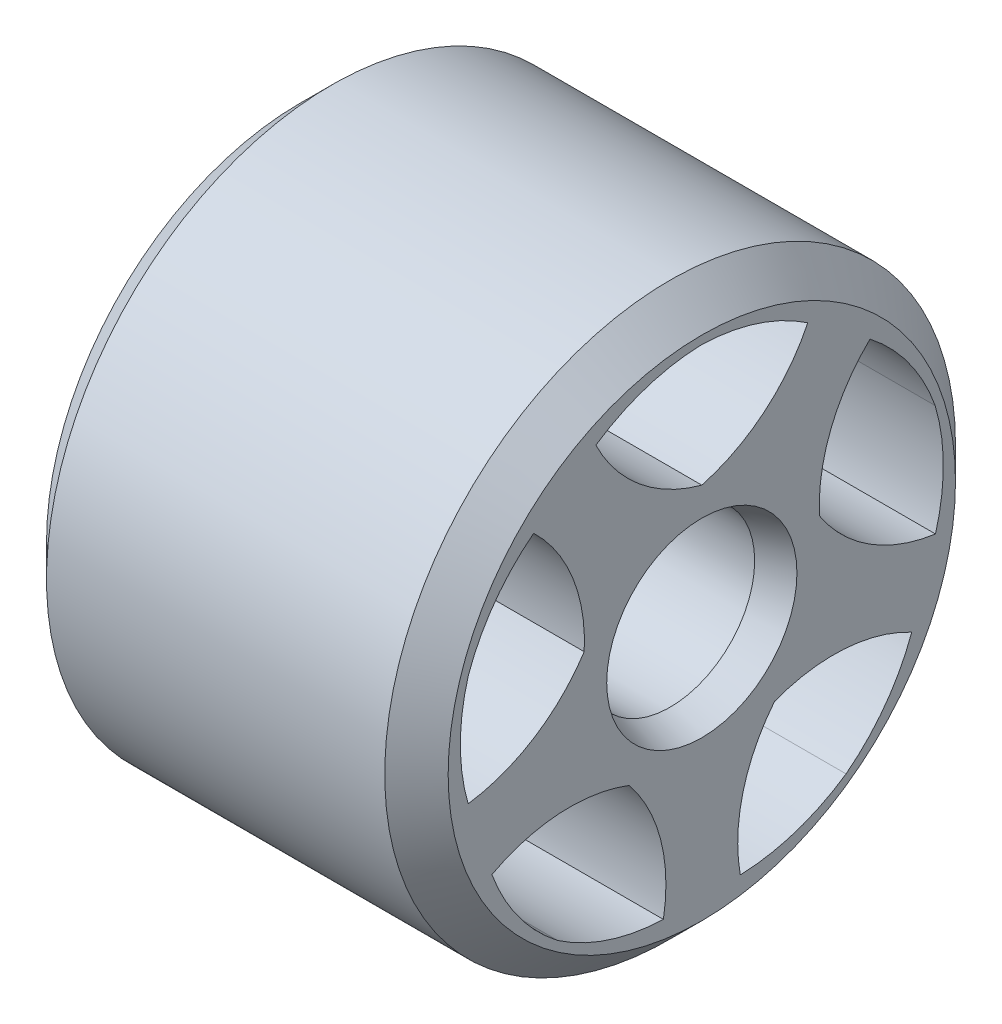
SolidWorks part; units mm, degrees
ref_plane "Front Plane" through (0, 0, 0) normal (0, 0, 1) x (1, 0, 0)
ref_plane "Top Plane" through (0, 0, 0) normal (0, 1, 0) x (1, 0, 0)
ref_plane "Right Plane" through (0, 0, 0) normal (1, 0, 0) x (0, 0, -1)
sketch "Sketch1" plane through (0, 0, 0) normal (1, 0, 0) x (0, 0, -1)
  circle A0 centre (0, 0) radius 13.5
  circle A1 centre (0, 0) radius 4
  dimension "D1" = 27
  dimension "D2" = 8
extrude "Boss-Extrude1" add sketch "Sketch1" along normal mid plane 19
sketch "Sketch2" plane through (0, 0, 0) normal (1, 0, 0) x (0, 0, -1)
  line L0 (0, 0) -> (0, 14.8201) construction
  arc A0 (0, 5.8497) -> (-5.0122, 9.994) centre (2.0377, 13.4173) cw
  arc A1 (-5.0122, 9.994) -> (0, 11.6087) centre (0.2591, 2.218) cw
  arc A2 (5.0122, 9.994) -> (0, 11.6087) centre (-0.2591, 2.218) ccw
  arc A3 (0, 5.8497) -> (5.0122, 9.994) centre (-2.0377, 13.4173) ccw
extrude "Cut-Extrude1" cut sketch "Sketch2" along normal through all both and the other way through all
pattern_circular "CirPattern1" count 5 over 360 about axis through (9.5, 0, 0) along (-1, 0, 0) of "Cut-Extrude1" reverse direction yes
chamfer "Chamfer1" distance 1.5 angle 45 2 edges at (9.5, 0, -13.5) (-9.5, 0, -13.5)
sketch "Sketch4" plane through (0, 0, 0) normal (1, 0, 0) x (0, 0, -1)
  circle A0 centre (0, 0) radius 13.5
  circle A1 centre (0, 0) radius 13.2
  circle A2 centre (0, 0) radius 13.5 construction
  dimension "D1" = 0.3
chamfer "Chamfer2" distance 0.5 distance2 1.5 1 edges at (9.5, 0, -4) first distance on face at (9.5, 0, -12)
equation "\"axis_diameter\"=5.66"
equation "\"padding\"=0.5"
